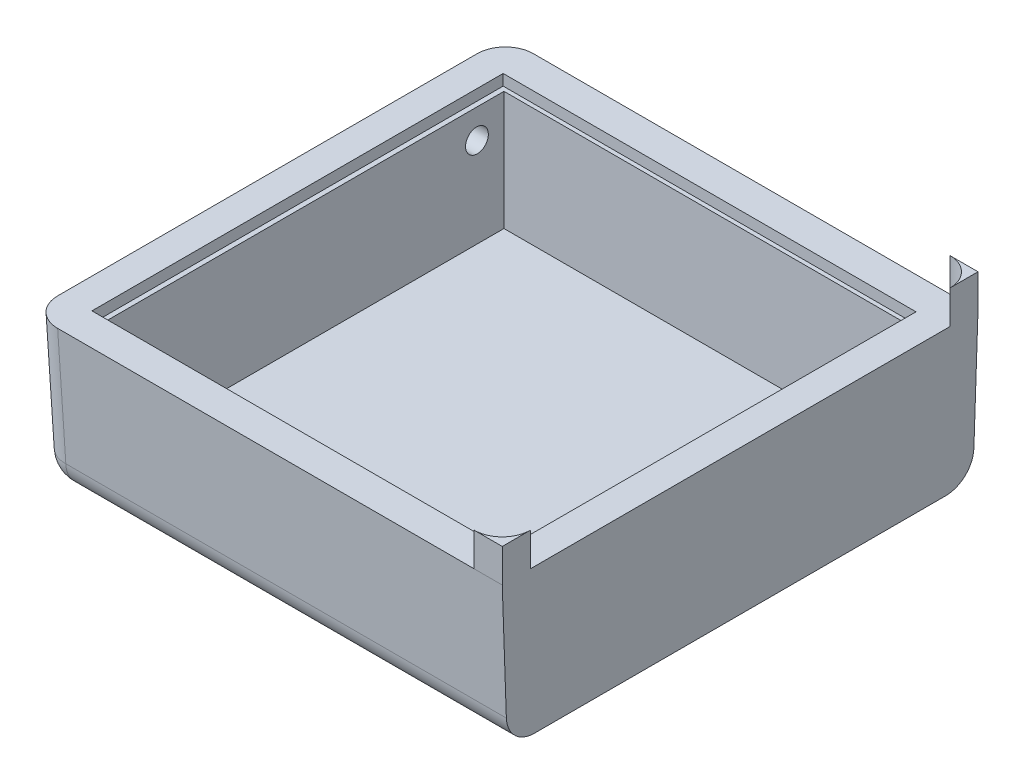
SolidWorks part; units mm, degrees
ref_plane "Front Plane" through (0, 0, 0) normal (0, 0, 1) x (1, 0, 0)
ref_plane "Top Plane" through (0, 0, 0) normal (0, 1, 0) x (1, 0, 0)
ref_plane "Right Plane" through (0, 0, 0) normal (1, 0, 0) x (0, 0, -1)
sketch "Sketch1" plane through (0, 0, 0) normal (0, 1, 0) x (1, 0, 0)
  line L1 (-145.25, -146.05) -> (149.75, -146.05)
  line L2 (-145.25, -146.05) -> (-145.25, 146.05)
  line L3 (-145.25, 146.05) -> (149.75, 146.05)
  line L4 (149.75, -146.05) -> (149.75, 146.05)
  point P0 (-145.25, 0)
  dimension "D1" = 145.25
  dimension "D3" = 292.1
  dimension "D5" = 295
extrude "Boss-Extrude1" add sketch "Sketch1" against normal blind 88.69 draft 2
sketch "Sketch3" plane through (0, 0, 0) normal (0, 1, 0) x (1, 0, 0)
  line L1 (-126.75, -126.25) -> (126.75, -126.25)
  line L4 (126.75, 126.25) -> (126.75, -126.25)
  line L9 (-126.75, 126.25) -> (-126.75, -126.25)
  line L183 (-126.75, 126.25) -> (126.75, 126.25)
  point P1 (-126.75, 0)
  dimension "D2" = 253.5
  dimension "D3" = 126.75
  dimension "D1" = 252.5
extrude "Cut-Extrude3" cut sketch "Sketch3" against normal blind 6.5 draft 2
sketch "Sketch5" plane through (0, -6.5, 0) normal (0, 1, 0) x (1, 0, 0)
  line L1 (-123.5, -123.5) -> (123.5, -123.5)
  line L2 (-123.5, -123.5) -> (-123.5, 123.5)
  line L3 (-123.5, 123.5) -> (123.5, 123.5)
  line L4 (123.5, -123.5) -> (123.5, 123.5)
  line L5 (-123.5, -123.5) -> (123.5, 123.5) construction
  line L6 (-123.5, 123.5) -> (123.5, -123.5) construction
  point P0 (0, 0)
  dimension "D1" = 247
extrude "Cut-Extrude4" cut sketch "Sketch5" against normal blind 70.5 draft 2
sketch "Sketch6" plane through (0, 0, 0) normal (0, 0, 1) x (1, 0, 0)
  line L0 (149.75, 0) -> (145, 0)
  line L1 (-145.25, 0) -> (149.75, 0) construction
  line L2 (145, 0) -> (145, -88.69)
  line L3 (-142.1529, -88.69) -> (146.6529, -88.69) construction
  line L4 (145, -88.69) -> (146.6529, -88.69)
  line L5 (146.6529, -88.69) -> (149.75, 0)
  dimension "D1" = 4.75
extrude "Cut-Extrude5" cut sketch "Sketch6" against normal through all both and the other way through all
fillet "Fillet2" radius 17.27 5 edges at (1.4236, -88.69, -142.9529) (-143.7014, -44.345, -144.5014) (-142.1529, -88.69, 0) (-143.7014, -44.345, 144.5014) (1.4236, -88.69, 142.9529)
sketch "Sketch7" plane through (0, 0, 0) normal (0, 1, 0) x (1, 0, 0)
  line L0 (-31.4885, 0) -> (69.7112, 0) construction
  line L1 (145, 146.05) -> (-127.9905, 146.05) construction
  line L2 (145, 146.05) -> (145, -146.05) construction
  line L3 (145, 128.78) -> (145, 146.05)
  line L4 (145, 146.05) -> (127.73, 146.05)
  line L5 (145, -146.05) -> (127.73, -146.05)
  line L6 (145, -128.78) -> (145, -146.05)
  arc A0 (127.73, 146.05) -> (145, 128.78) centre (127.73, 128.78) cw
  arc A1 (127.73, -146.05) -> (145, -128.78) centre (127.73, -128.78) ccw
  dimension "D1" = 17.27
extrude "Boss-Extrude2" add sketch "Sketch7" along normal blind 20.53
sketch "Sketch8" plane through (-145.0731, -5.0661, 0) normal (-0.9994, -0.0349, 0) x (0, 0, 1)
  line L0 (-128.7905, 5.0692) -> (128.7905, 5.0692) construction
  line L3 (-123.5, -10.8061) -> (-123.5, -2.186) construction
  circle A0 centre (-106.3, -19.4008) radius 7
  dimension "D3" = 14
  dimension "D1" = 24.47
  dimension "D2" = 17.2
extrude "Cut-Extrude6" cut sketch "Sketch8" against normal up to next
